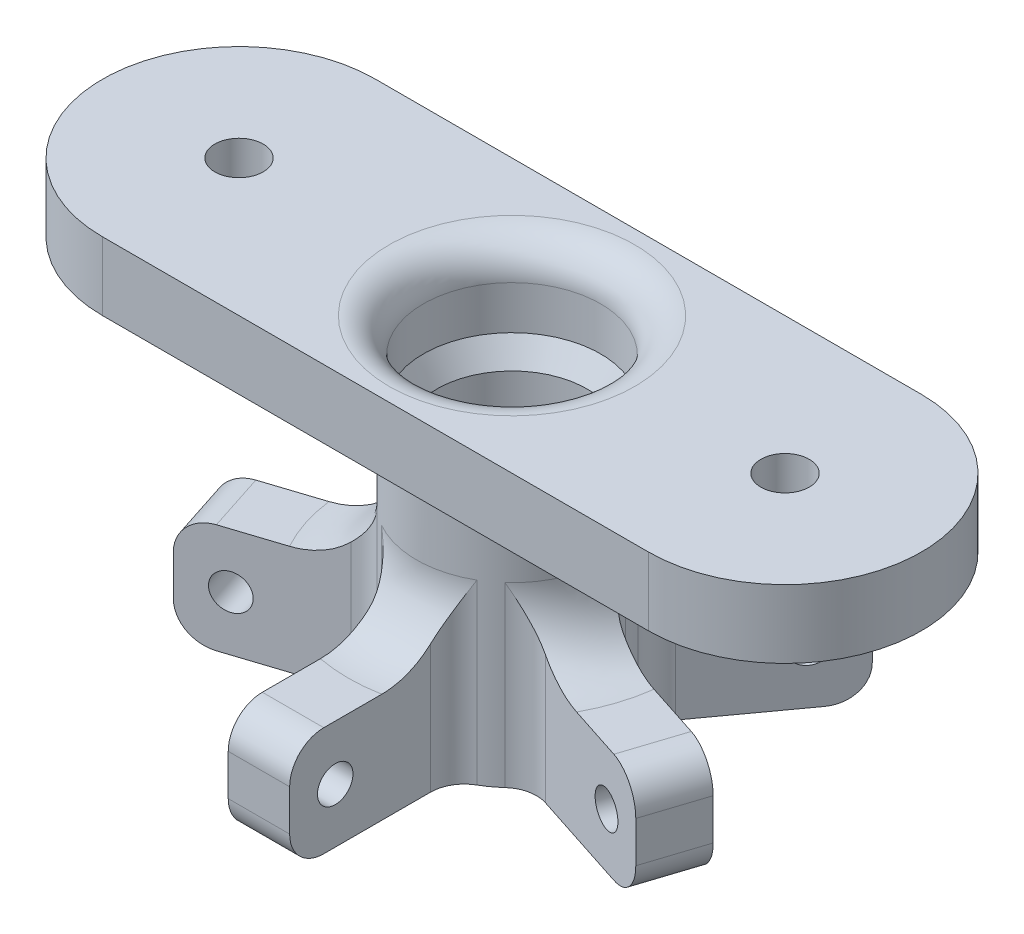
SolidWorks part; units mm, degrees
material "ABS PC"
ref_plane "Front Plane" through (0, 0, 0) normal (0, 0, 1) x (1, 0, 0)
ref_plane "Top Plane" through (0, 0, 0) normal (0, 1, 0) x (1, 0, 0)
ref_plane "Right Plane" through (0, 0, 0) normal (1, 0, 0) x (0, 0, -1)
sketch "Sketch1" plane through (0, 0, 0) normal (0, 1, 0) x (1, 0, 0)
  circle A0 centre (0, 0) radius 6.985
  circle A1 centre (0, 0) radius 8.89
extrude "Boss-Extrude1" add sketch "Sketch1" along normal blind 25.4
sketch "Sketch3" plane through (0, 0, 0) normal (0, -1, 0) x (1, 0, 0)
  line L0 (7.1232, 5.319) -> (21.5084, 9.993)
  line L1 (-2.8575, 8.4182) -> (-2.8575, 23.5437)
  line L2 (21.5084, 9.993) -> (23.2744, 4.5578)
  line L3 (-2.8575, 23.5437) -> (2.8575, 23.5437)
  line L4 (2.8575, 23.5437) -> (2.8575, 8.4182)
  line L5 (23.2744, 4.5578) -> (8.8892, -0.1163)
  line L6 (7.2599, -5.1309) -> (16.1504, -17.3677)
  line L7 (16.1504, -17.3677) -> (11.5269, -20.7269)
  line L8 (11.5269, -20.7269) -> (2.6364, -8.4901)
  line L9 (-2.6364, -8.4901) -> (-11.5269, -20.7269)
  line L10 (-11.5269, -20.7269) -> (-16.1504, -17.3677)
  line L11 (-16.1504, -17.3677) -> (-7.2599, -5.1309)
  line L12 (-8.8892, -0.1163) -> (-23.2744, 4.5578)
  line L13 (-23.2744, 4.5578) -> (-21.5084, 9.993)
  line L14 (-21.5084, 9.993) -> (-7.1232, 5.319)
  circle A0 centre (0, 0) radius 8.89 construction
  arc A1 (2.8575, 8.4182) -> (-2.8575, 8.4182) centre (0, 0) ccw
  arc A2 (8.8892, -0.1163) -> (7.1232, 5.319) centre (0, 0) ccw
  arc A3 (2.6364, -8.4901) -> (7.2599, -5.1309) centre (0, 0) ccw
  arc A4 (-7.2599, -5.1309) -> (-2.6364, -8.4901) centre (0, 0) ccw
  arc A5 (-7.1232, 5.319) -> (-8.8892, -0.1163) centre (0, 0) ccw
  point P26 (0, 0)
  dimension "D1" = 5
  dimension "D2" = 5.715
extrude "Boss-Extrude2" add sketch "Sketch3" against normal blind 10.16
sketch "Sketch4" plane through (0.883, 0, 2.7176) normal (0.309, 0, 0.9511) x (0.9511, 0, -0.309)
  circle A0 centre (-19.304, 5.08) radius 1.651
extrude "Cut-Extrude1" cut sketch "Sketch4" against normal up to next
pattern_circular "CirPattern1" count 5 over 360 about axis through (0, 25.4, 0) along (0, -1, 0) of "Cut-Extrude1"
fillet "Fillet1" radius 6.35 5 edges at (5.2254, 10.16, -7.1922) (-5.2254, 10.16, -7.1922) (8.4549, 10.16, 2.7472) (0, 10.16, 8.89) (-8.4549, 10.16, 2.7472)
fillet "Fillet2" radius 3.175 20 edges at (0, 0, 23.5437) (0, 10.16, 23.5437) (-22.3914, 0, 7.2754) (-22.3914, 10.16, 7.2754) (-13.8386, 0, -19.0473) (-13.8386, 10.16, -19.0473) (13.8386, 10.16, -19.0473) (13.8386, 0, -19.0473) (22.3914, 0, 7.2754) (22.3914, 10.16, 7.2754) (7.2599, 8.255, -5.1309) (8.8892, 8.255, -0.1163) (-2.6364, 8.255, -8.4901) (2.6364, 8.255, -8.4901) (-8.8892, 8.255, -0.1163) (-7.2599, 8.255, -5.1309) (-7.1232, 8.255, 5.319) (-2.8575, 8.255, 8.4182) (7.1232, 8.255, 5.319) (2.8575, 8.255, 8.4182)
sketch "Sketch5" plane through (0, 25.4, 0) normal (0, 1, 0) x (1, 0, 0)
  line L2 (-25.4, 12.7) -> (25.4, 12.7)
  line L3 (25.4, -12.7) -> (-25.4, -12.7)
  circle A0 centre (0, 0) radius 6.985
  arc A1 (-25.4, 12.7) -> (-25.4, -12.7) centre (-25.4, 0) ccw
  arc A2 (25.4, -12.7) -> (25.4, 12.7) centre (25.4, 0) ccw
extrude "Boss-Extrude3" add sketch "Sketch5" along normal blind 6.35
fillet "Fillet3" radius 3.175 1 edges at (0, 25.4, 8.89)
sketch "Sketch6" plane through (0, 31.75, 0) normal (0, 1, 0) x (1, 0, 0)
  circle A0 centre (25.4, 0) radius 2.25
  circle A1 centre (-25.4, 0) radius 2.25
  dimension "D3" = 4.5
  dimension "D1" = 25.4
  dimension "D2" = 25.4
extrude "Cut-Extrude2" cut sketch "Sketch6" against normal blind 12.7
sketch "Sketch7" plane through (0, 31.75, 0) normal (0, 1, 0) x (1, 0, 0)
  circle A0 centre (0, 0) radius 8.25
extrude "Cut-Extrude3" cut sketch "Sketch7" against normal blind 5
fillet "Fillet5" radius 3.175 1 edges at (0, 31.75, 8.25)
chamfer "Chamfer1" distance 2.54 angle 60 1 edges at (0, 26.75, 6.985) first distance on face at (0, 26.75, 6.985)
